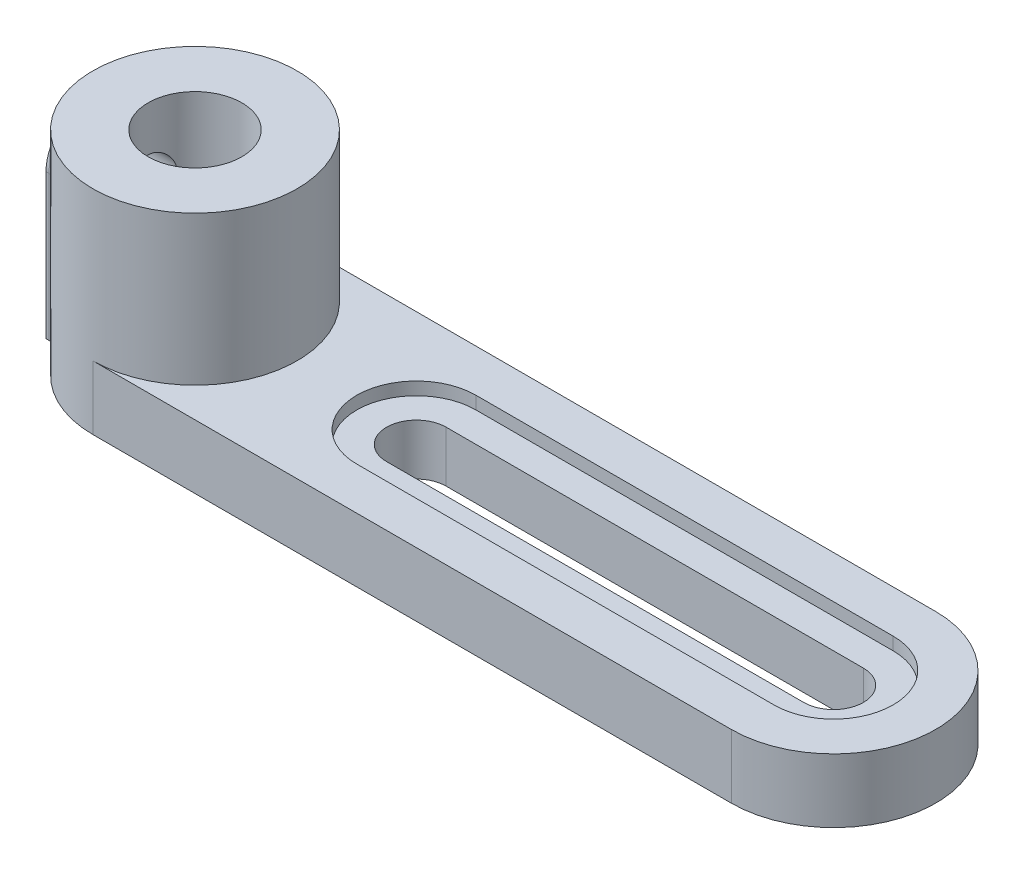
SolidWorks part; units mm, degrees
ref_plane "Front Plane" through (0, 0, 0) normal (0, 0, 1) x (1, 0, 0)
ref_plane "Top Plane" through (0, 0, 0) normal (0, 1, 0) x (1, 0, 0)
ref_plane "Right Plane" through (0, 0, 0) normal (1, 0, 0) x (0, 0, -1)
sketch "Sketch1" plane through (0, 0, 0) normal (0, 1, 0) x (1, 0, 0)
  line L0 (0, 0) -> (-150, 0) construction
  line L1 (0, -24) -> (-150, -24)
  line L2 (0, 24) -> (-150, 24)
  arc A0 (0, -24) -> (0, 24) centre (0, 0) ccw
  arc A1 (-150, 24) -> (-150, -24) centre (-150, 0) ccw
  point P3 (-75, 0)
  dimension "D1" = 24
  dimension "D2" = 150
extrude "Boss-Extrude1" add sketch "Sketch1" along normal blind 15
sketch "Sketch2" plane through (0, 15, 0) normal (0, 1, 0) x (1, 0, 0)
  circle A0 centre (-150, 0) radius 24
  arc A1 (-150, 24) -> (-150, -24) centre (-150, 0) ccw construction
extrude "Boss-Extrude2" add sketch "Sketch2" along normal blind 35
sketch "Sketch3" plane through (0, 15, 0) normal (0, 1, 0) x (1, 0, 0)
  line L0 (0, 0) -> (-98, 0) construction
  line L1 (0, -7) -> (-98, -7)
  line L2 (0, 7) -> (-98, 7)
  arc A0 (0, -7) -> (0, 7) centre (0, 0) ccw
  arc A1 (-98, 7) -> (-98, -7) centre (-98, 0) ccw
  point P3 (-49, 0)
  dimension "D1" = 7
  dimension "D2" = 98
extrude "Cut-Extrude1" cut sketch "Sketch3" against normal up to next
sketch "Sketch4" plane through (0, 15, 0) normal (0, 1, 0) x (1, 0, 0)
  line L0 (0, 0) -> (-98, 0) construction
  line L1 (0, -14) -> (-98, -14)
  line L2 (0, 14) -> (-98, 14)
  arc A0 (0, -14) -> (0, 14) centre (0, 0) ccw
  arc A1 (-98, 14) -> (-98, -14) centre (-98, 0) ccw
  point P4 (-49, 0)
  dimension "D1" = 14
extrude "Cut-Extrude2" cut sketch "Sketch4" against normal blind 3
ref_plane "Plane1" through (-175, 0, 0) normal (1, 0, 0) x (0, 0, -1)
sketch "Sketch5" plane through (-175, 0, 0) normal (1, 0, 0) x (0, 0, -1)
  line L0 (-10, 34) -> (-10, 0)
  line L1 (-24, 0) -> (24, 0) construction
  line L2 (-10, 0) -> (10, 0)
  line L3 (10, 0) -> (10, 34)
  arc A0 (10, 34) -> (-10, 34) centre (0, 34) ccw
  dimension "D1" = 20
  dimension "D2" = 34
extrude "Boss-Extrude3" add sketch "Sketch5" along normal up to next
hole_wizard "Hole1" positions "Sketch6" profile "Sketch7" legacy end condition through all
sketch "Sketch6" plane through (0, 50, 0) normal (0, 1, 0) x (1, 0, 0)
  point P0 (-150, 0)
sketch "Sketch7" plane through (-150, 50, 0) normal (1, 0, 0) x (0, 0, 1)
  line L0 (0, 0) -> (0, 50)
  line L1 (0, 50) -> (11, 50)
  line L2 (11, 50) -> (11, 0)
  line L3 (11, 0) -> (0, 0)
  line L4 (0, 110) -> (0, -10) construction
  dimension "Diameter" = 22
  dimension "Depth" = 50
hole_wizard "M12x1.25 Tapped Hole1" positions "Sketch8" profile "Sketch9" tap size "M12x1.25" standard "ANSI Metric" end condition up to next
sketch "Sketch8" plane through (-175, 0, 0) normal (-1, 0, 0) x (0, 0, 1)
  point P0 (0, 34)
sketch "Sketch9" plane through (-175, 34, 0) normal (0, 1, 0) x (0, 0, 1)
  line L0 (0, 0) -> (0, 14)
  line L1 (0, 14) -> (5.4, 14)
  line L2 (5.4, 14) -> (5.4, 0.5244)
  line L3 (5.4, 0.5244) -> (6.025, 0)
  line L5 (6.025, 0) -> (0, 0)
  line L6 (-5.4, 0.5244) -> (-6.025, 0) construction
  line L11 (0, -6.35) -> (0, 107.95) construction
  dimension "Thru Tap Drill Dia." = 10.8
  dimension "Thru Tap Drill Depth" = 14
  dimension "Near C'Sink Dia." = 12.05
  dimension "Near C'Sink Angle" = 100
cosmetic thread "Hole Thread1" parameters "D2"=12
fillet "Fillet1" radius 4 3 edges at (-171.8174, 17, -10) (-171.8174, 17, 10) (-173.988, 43.9713, 0.7573)
